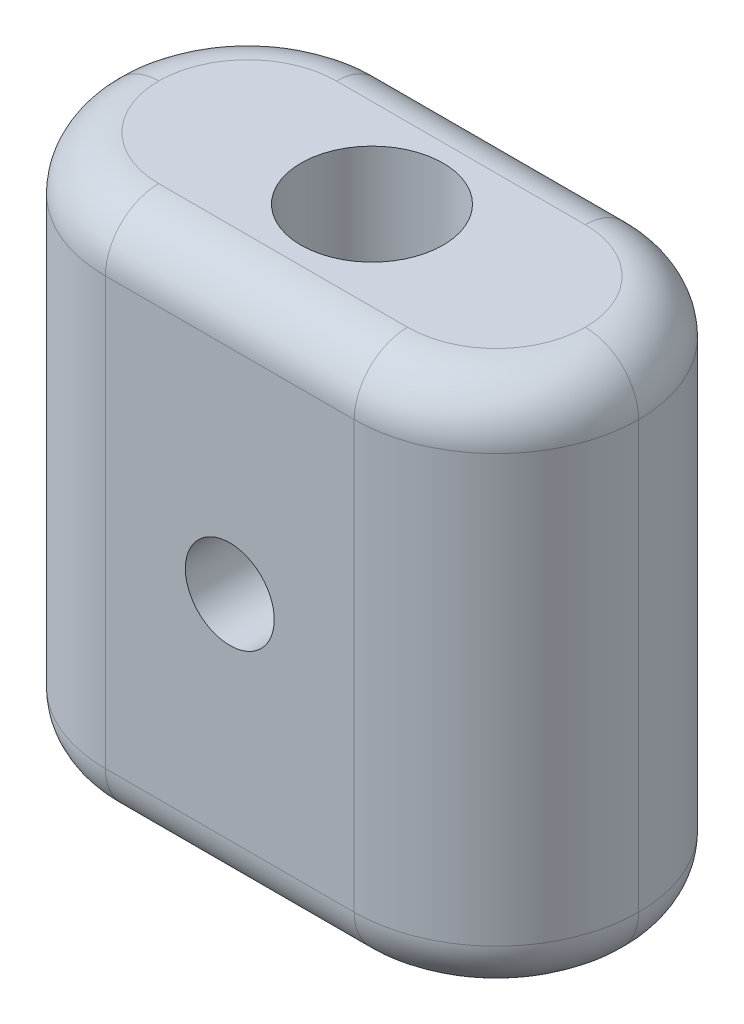
SolidWorks part; units mm, degrees
ref_plane "Front Plane" through (0, 0, 0) normal (0, 0, 1) x (1, 0, 0)
ref_plane "Top Plane" through (0, 0, 0) normal (0, 1, 0) x (1, 0, 0)
ref_plane "Right Plane" through (0, 0, 0) normal (1, 0, 0) x (0, 0, -1)
sketch "Sketch1" plane through (0, 0, 0) normal (0, 0, 1) x (1, 0, 0)
  line L1 (0, 0) -> (30, 0)
  line L2 (0, 0) -> (0, 30)
  line L3 (0, 30) -> (30, 30)
  line L4 (30, 0) -> (30, 30)
extrude "Boss-Extrude1" add sketch "Sketch1" along normal blind 16
sketch "Sketch2" plane through (0, 0, 0) normal (0, 0, -1) x (-1, 0, 0)
  line L0 (-15, 30) -> (-15, 0) construction
  line L1 (-30, 30) -> (0, 30) construction
  line L2 (0, 0) -> (-30, 0) construction
  circle A0 centre (-15, 15) radius 2.5
extrude "Cut-Extrude1" cut sketch "Sketch2" against normal through all
sketch "Sketch3" plane through (0, 30, 0) normal (0, 1, 0) x (1, 0, 0)
  line L0 (15, -16) -> (15, 0) construction
  line L1 (30, -16) -> (0, -16) construction
  line L2 (30, 0) -> (0, 0) construction
  circle A0 centre (15, -8) radius 4
extrude "Cut-Extrude2" cut sketch "Sketch3" against normal through all
fillet "Fillet1" radius 8 4 edges at (30, 15, 0) (30, 15, 16) (0, 15, 0) (0, 15, 16)
fillet "Fillet2" radius 3 12 edges at (2.3431, 0, 13.6569) (2.3431, 0, 2.3431) (15, 0, 0) (27.6569, 0, 2.3431) (27.6569, 0, 13.6569) (27.6569, 30, 13.6569) (27.6569, 30, 2.3431) (15, 30, 0) (2.3431, 30, 2.3431) (2.3431, 30, 13.6569) (15, 0, 16) (15, 30, 16)
